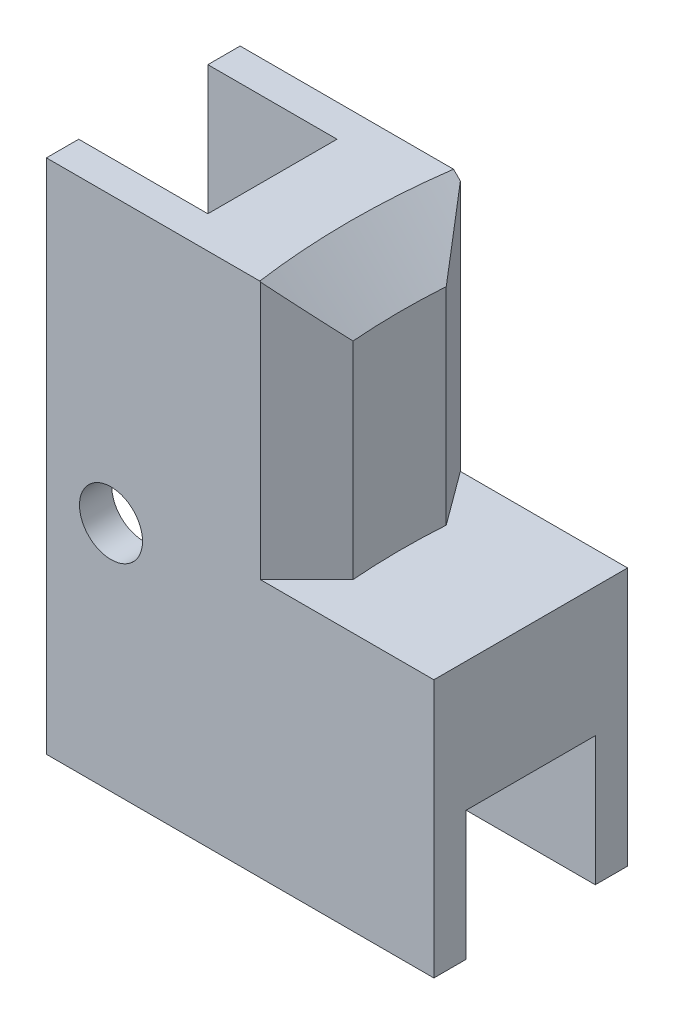
SolidWorks part; units mm, degrees
ref_plane "Front Plane" through (0, 0, 0) normal (0, 0, 1) x (1, 0, 0)
ref_plane "Top Plane" through (0, 0, 0) normal (0, 1, 0) x (1, 0, 0)
ref_plane "Right Plane" through (0, 0, 0) normal (1, 0, 0) x (0, 0, -1)
sketch "Sketch1" plane through (0, 0, 0) normal (0, 0, 1) x (1, 0, 0)
  line L0 (-44.45, 19.05) -> (-44.45, -6.35)
  line L1 (-44.45, -6.35) -> (-25.4, -6.35)
  line L2 (-25.4, -6.35) -> (-25.4, 6.35)
  line L3 (-25.4, 6.35) -> (-28.575, 6.35)
  line L4 (-28.575, 6.35) -> (-28.575, 19.05)
  line L5 (-28.575, 19.05) -> (-44.45, 19.05)
  line L8 (0, -988.495) -> (0, 49011.505) construction
  line L9 (-38.1, 19.05) -> (-38.1, -6.35) construction
  line L10 (-38.1, 0) -> (-25.4, 0) construction
  line L11 (13.97, 0) -> (-13.97, 0) construction
  point P7 (-50.8, -6.35)
  dimension "D1" = 101.6
  dimension "D2" = 6.35
  dimension "D3" = 9.525
  dimension "D4" = 12.7
  dimension "D6" = 19.05
  dimension "D7" = 12.7
  dimension "D8" = 6.35
  dimension "D9" = 6.35
extrude "Boss-Extrude1" add sketch "Sketch1" along normal mid plane 9.525
sketch "Sketch2" plane through (0, 0, 0) normal (0, 0, 1) x (1, 0, 0)
  line L0 (-44.45, 19.05) -> (-38.1, 19.05)
  line L1 (-38.1, 19.05) -> (-38.1, 0)
  line L2 (-38.1, 0) -> (-25.4, 0)
  line L3 (-25.4, 0) -> (-25.4, -6.35)
  line L4 (-25.4, -6.35) -> (-44.45, -6.35)
  line L5 (-44.45, -6.35) -> (-44.45, 19.05)
  line L7 (-28.575, 19.05) -> (-44.45, 19.05) construction
  line L8 (-44.45, 19.05) -> (-44.45, -6.35) construction
  line L9 (13.97, 0) -> (-13.97, 0) construction
  line L10 (-44.45, -6.35) -> (-25.4, -6.35) construction
  line L11 (-25.4, -6.35) -> (-25.4, 6.35) construction
  line L12 (-38.1, 19.05) -> (-38.1, -6.35) construction
extrude "Cut-Extrude1" cut sketch "Sketch2" against normal mid plane 6.35
fillet "Fillet1" radius 3.302 1 edges at (-38.1, 0, 0)
sketch "Sketch3" plane through (0, 19.05, 0) normal (0, 1, 0) x (1, 0, 0)
  circle A0 centre (0, 0) radius 31.75
  dimension "D1" = 63.5
extrude "Cut-Extrude2" cut sketch "Sketch3" against normal up to surface (12.7 mm away) up to face at (-26.9875, 6.35, 0)
chamfer "Chamfer1" distance 2.54 angle 45 3 edges at (-31.75, 19.05, 0) (-31.3908, 12.7, 4.7625) (-31.3908, 12.7, -4.7625)
sketch "Sketch4" plane through (0, 0, 4.7625) normal (0, 0, 1) x (1, 0, 0)
  line L0 (-38.1, 0) -> (-25.4, 0) construction
  circle A0 centre (-41.275, 5.08) radius 1.55
  dimension "D1" = 5.08
  dimension "D2" = 3.1
  dimension "D3" = 9.525
extrude "Cut-Extrude3" cut sketch "Sketch4" against normal through all
